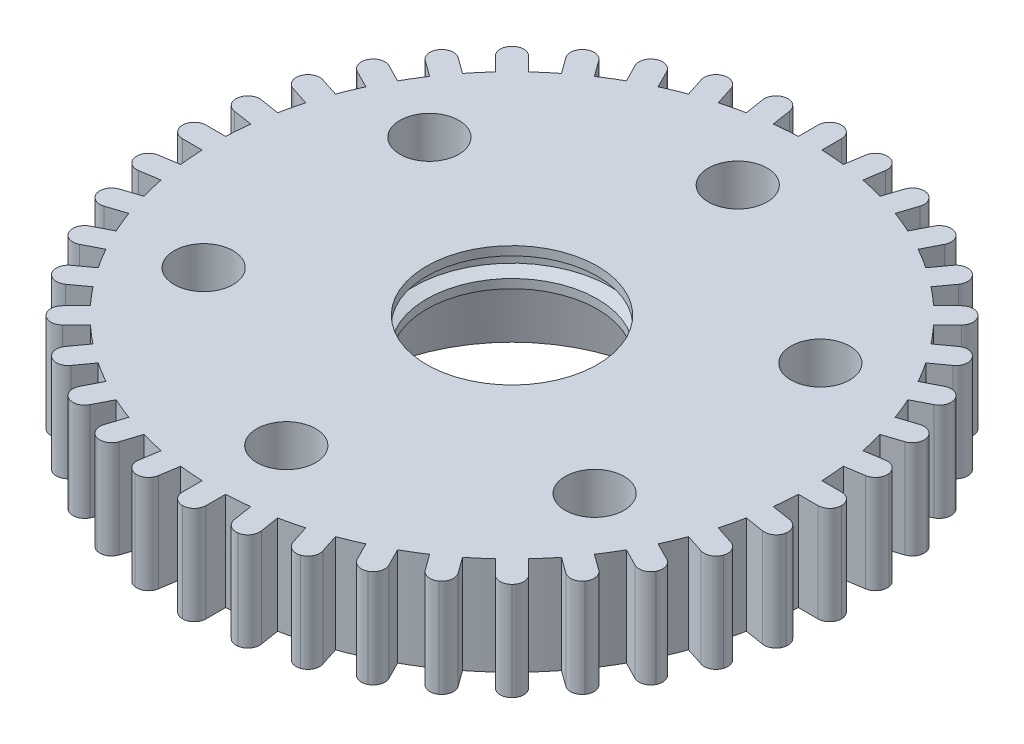
SolidWorks part; units mm, degrees
ref_plane "前视基准面" through (0, 0, 0) normal (0, 0, 1) x (1, 0, 0)
ref_plane "上视基准面" through (0, 0, 0) normal (0, 1, 0) x (1, 0, 0)
ref_plane "右视基准面" through (0, 0, 0) normal (1, 0, 0) x (0, 0, -1)
sketch "草图1" plane through (0, 0, 0) normal (0, 0, 1) x (0, 1, 0)
  line L0 (-1000, 0) -> (49000, 0) construction
  line L1 (0, -1000) -> (0, 49000) construction
  line L2 (0, 152) -> (0, 43.5)
  line L3 (0, 43.5) -> (-4.5, 43.5)
  line L4 (-4.5, 43.5) -> (-6.5, 50.25)
  line L5 (-6.5, 50.25) -> (-12.5, 50.25)
  line L6 (-12.5, 50.25) -> (-14.5, 43.5)
  line L7 (-14.5, 43.5) -> (-19, 43.5)
  line L8 (-9.5, -945.5361) -> (-9.5, 49054.4639) construction
  line L9 (-19, 43.5) -> (-24, 72.5)
  line L10 (-24, 72.5) -> (-67, 78)
  line L11 (-67, 78) -> (-67, 85)
  line L12 (-67, 85) -> (-57, 85)
  line L13 (-57, 85) -> (-57, 140)
  line L14 (-57, 140) -> (-50, 140)
  line L15 (-50, 140) -> (-50, 152)
  line L16 (-50, 152) -> (0, 152)
  point P15 (-9.5, 50.25)
  dimension "D1" = 43.5
  dimension "D2" = 4.5
  dimension "D3" = 4.5
  dimension "D4" = 10
  dimension "D5" = 50.25
  dimension "D6" = 6
  dimension "D7" = 48
  dimension "D8" = 43
  dimension "D9" = 72.5
  dimension "D10" = 78
  dimension "D11" = 85
  dimension "D12" = 57
  dimension "D13" = 140
  dimension "D14" = 50
  dimension "D15" = 152
revolve "旋转1" add sketch "草图1" angle 360 about L0
sketch "草图2" plane through (0, 0, 0) normal (0, -1, 0) x (1, 0, 0)
  line L0 (0, -1000) -> (0, 49000) construction
  circle A0 centre (0, 115) radius 8.5
  dimension "D1" = 17
  dimension "D2" = 115
extrude "切除-拉伸5" cut sketch "草图2" along normal through all
sketch "草图4" plane through (0, 0, 0) normal (0, 1, 0) x (1, 0, 0)
  circle A0 centre (0, -115) radius 15
  circle A1 centre (0, -115) radius 8.5 construction
  dimension "D1" = 30
extrude "切除-拉伸6" cut sketch "草图4" against normal blind 25
pattern_circular "阵列(圆周)1" count 6 over 360 about axis through (0, 0, 0) along (0, 1, 0) of "切除-拉伸5", "切除-拉伸6"
sketch "草图5" plane through (0, 0, 0) normal (0, 1, 0) x (1, 0, 0)
  line L0 (0, -1000) -> (0, 49000) construction
  line L1 (-963.6258, 152) -> (49036.3742, 152) construction
  line L2 (-6, 167.8815) -> (-6, 151.8815)
  line L3 (-6, 167.8815) -> (6, 167.8815)
  line L4 (6, 167.8815) -> (6, 151.8815)
  circle A0 centre (0, 0) radius 152 construction
  arc A1 (-6, 151.8815) -> (6, 151.8815) centre (0, 0) cw
  dimension "D1" = 16
  dimension "D2" = 12
extrude "凸台-拉伸1" add sketch "草图5" against normal blind 50
fillet "圆角1" radius 6 2 edges at (-6, -25, -167.8815) (6, -25, -167.8815)
pattern_circular "阵列(圆周)2" count 40 over 360 about axis through (0, 0, 0) along (0, 1, 0) of "圆角1", "凸台-拉伸1"
